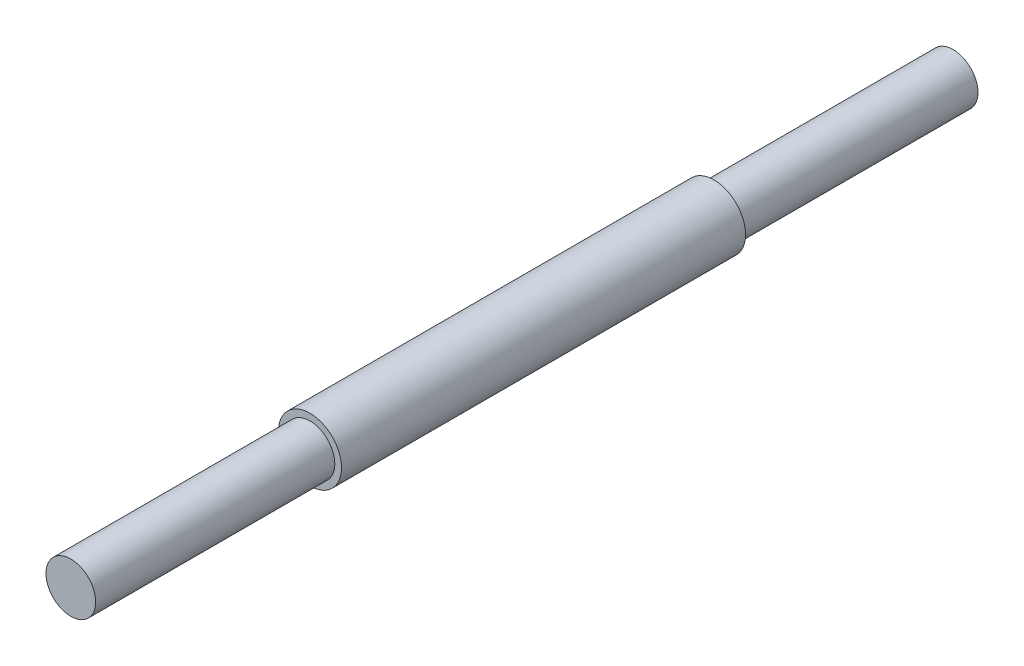
SolidWorks part; units mm, degrees
ref_plane "Front Plane" through (0, 0, 0) normal (0, 0, 1) x (1, 0, 0)
ref_plane "Top Plane" through (0, 0, 0) normal (0, 1, 0) x (1, 0, 0)
ref_plane "Right Plane" through (0, 0, 0) normal (1, 0, 0) x (0, 0, -1)
sketch "Sketch2" plane through (0, 0, 0) normal (0, 0, 1) x (1, 0, 0)
  circle A0 centre (0, 0) radius 2.5
  dimension "D1" = 5
extrude "Boss-Extrude1" add sketch "Sketch2" along normal blind 44.3738 and the other way blind 44.3738
sketch "Sketch3" plane through (0, 0, 0) normal (0, 0, 1) x (1, 0, 0)
  circle A0 centre (0, 0) radius 3.175
  dimension "D1" = 6.35
extrude "Boss-Extrude2" add sketch "Sketch3" along normal blind 20.32 and the other way blind 20.32
